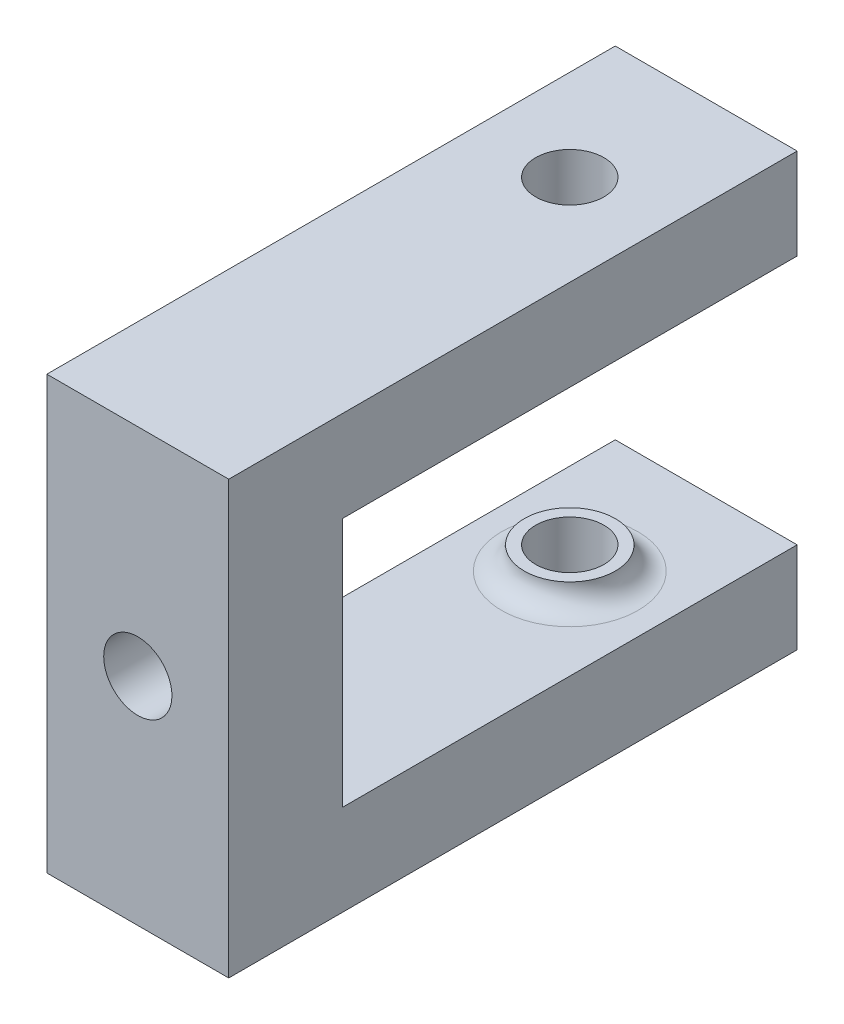
SolidWorks part; units mm, degrees
ref_plane "Спереди" through (0, 0, 0) normal (0, 0, 1) x (1, 0, 0)
ref_plane "Сверху" through (0, 0, 0) normal (0, 1, 0) x (1, 0, 0)
ref_plane "Справа" through (0, 0, 0) normal (1, 0, 0) x (0, 0, -1)
sketch "Эскиз3" plane through (0, 0, 0) normal (1, 0, 0) x (0, 0, -1)
  line L0 (0, 0) -> (25, 0)
  line L1 (25, 0) -> (25, 4)
  line L2 (25, 4) -> (5, 4)
  line L3 (5, 4) -> (5, 15)
  line L4 (5, 15) -> (25, 15)
  line L5 (25, 15) -> (25, 19)
  line L6 (25, 19) -> (0, 19)
  line L7 (0, 19) -> (0, 0)
  dimension "D1" = 4
  dimension "D2" = 4
  dimension "D3" = 11
  dimension "D4" = 5
  dimension "D5" = 25
extrude "Бобышка-Вытянуть1" add sketch "Эскиз3" along normal blind 8
sketch "Эскиз4" plane through (0, 19, 0) normal (0, 1, 0) x (1, 0, 0)
  line L0 (4, 25) -> (4, 0) construction
  line L1 (8, 25) -> (0, 25) construction
  line L2 (8, 0) -> (0, 0) construction
  circle A0 centre (4, 19) radius 1.5
  point P8 (0, 0)
  dimension "D2" = 3
  dimension "D1" = 6
extrude "Вырез-Вытянуть1" cut sketch "Эскиз4" against normal up to surface (19 mm away) up to face at (4, 0, -12.5)
sketch "Эскиз5" plane through (0, 4, 0) normal (0, 1, 0) x (1, 0, 0)
  circle A0 centre (4, 19) radius 2
  circle A1 centre (4, 19) radius 1.5
  dimension "D1" = 4
  dimension "D2" = 3
extrude "Бобышка-Вытянуть2" add sketch "Эскиз5" along normal blind 1
sketch "Эскиз6" plane through (0, 15, 0) normal (0, -1, 0) x (-1, 0, 0)
  circle A0 centre (-4, 19) radius 2
  circle A1 centre (-4, 19) radius 1.5
  dimension "D1" = 4
  dimension "D2" = 3
extrude "Бобышка-Вытянуть3" add sketch "Эскиз6" along normal blind 1
fillet "Скругление1" radius 1 1 edges at (4, 4, -21)
fillet "Скругление2" radius 1 1 edges at (4, 15, -17)
sketch "Эскиз7" plane through (0, 0, -5) normal (0, 0, -1) x (-1, 0, 0)
  line L0 (-8, 9.5) -> (0, 9.5) construction
  line L1 (-8, 4) -> (-8, 15) construction
  line L2 (0, 4) -> (0, 15) construction
  line L3 (-4, 15) -> (-4, 4) construction
  line L4 (-8, 15) -> (0, 15) construction
  line L5 (-8, 4) -> (0, 4) construction
  circle A0 centre (-4, 9.5) radius 1.5
  dimension "D1" = 3
extrude "Вырез-Вытянуть2" cut sketch "Эскиз7" against normal up to surface (5 mm away) up to face at (4, 9.5, 0)
sketch "Эскиз9" plane through (0, 0, -5) normal (0, 0, -1) x (-1, 0, 0)
  line L1 (-1.2641, 11.1119) -> (-4.028, 12.6753)
  line L2 (-4.028, 12.6753) -> (-6.7639, 11.0634)
  line L3 (-6.7639, 11.0634) -> (-6.7359, 7.8881)
  line L4 (-6.7359, 7.8881) -> (-3.972, 6.3247)
  line L5 (-3.972, 6.3247) -> (-1.2361, 7.9366)
  line L6 (-1.2361, 7.9366) -> (-1.2641, 11.1119)
  circle A0 centre (-4, 9.5) radius 2.75 construction
  dimension "D1" = 5.5
extrude "Вырез-Вытянуть3" cut sketch "Эскиз9" against normal blind 2
